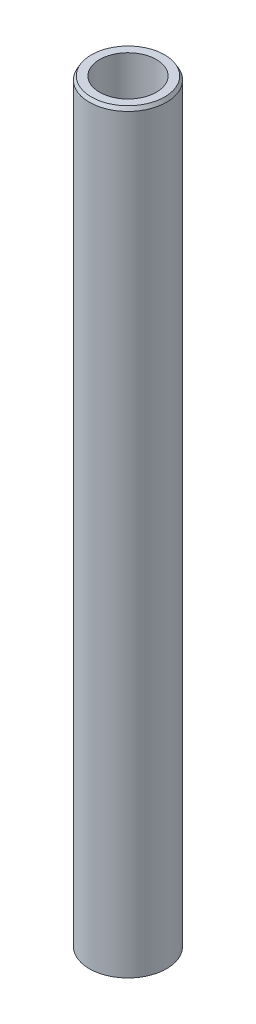
SolidWorks part; units mm, degrees
ref_plane "Front Plane" through (0, 0, 0) normal (0, 0, 1) x (1, 0, 0)
ref_plane "Top Plane" through (0, 0, 0) normal (0, 1, 0) x (1, 0, 0)
ref_plane "Right Plane" through (0, 0, 0) normal (1, 0, 0) x (0, 0, -1)
sketch "Sketch1" plane through (0, 0, 0) normal (0, 1, 0) x (1, 0, 0)
  circle A0 centre (0, 0) radius 25
  dimension "SHAFT_OD" = 50
extrude "Boss-Extrude1" add sketch "Sketch1" along normal blind 489.2479
sketch "Sketch2" plane through (0, 0, 0) normal (0, 1, 0) x (1, 0, 0)
  circle A0 centre (0, 0) radius 18.3747
  dimension "BORE_D" = 36.7494
extrude "Cut-Extrude1" cut sketch "Sketch2" along normal through all
chamfer "Chamfer1" distance 2.2759 angle 30 2 edges at (0, 489.2479, 25) (0, 0, 25) first distance on face at (0, 489.2479, 25) first distance on face at (0, 0, 18.3747)
